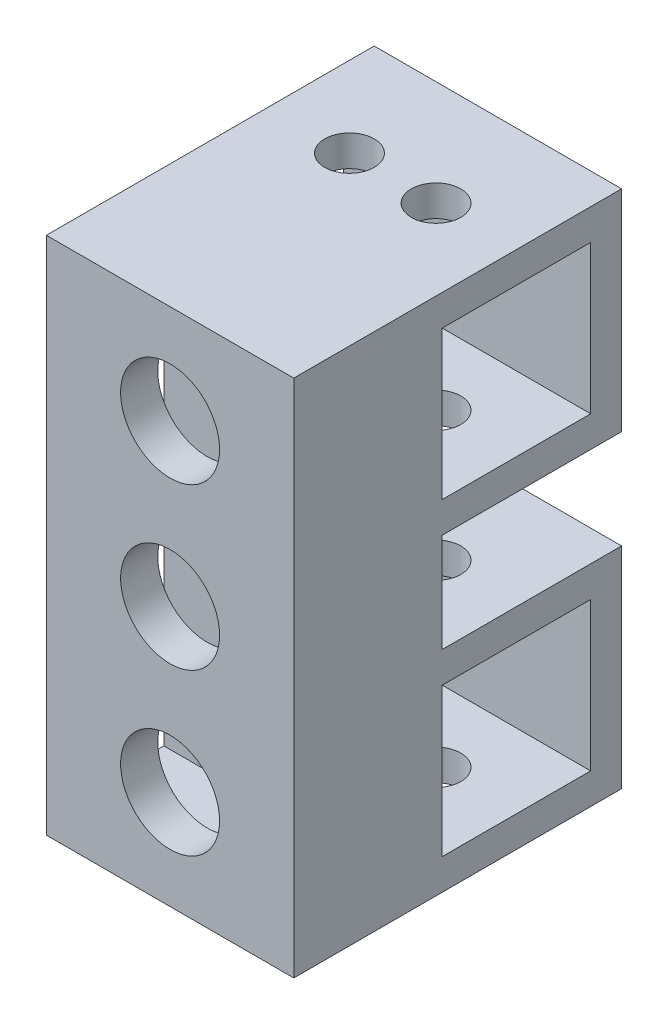
SolidWorks part; units mm, degrees
ref_plane "Plan de face" through (0, 0, 0) normal (0, 0, 1) x (1, 0, 0)
ref_plane "Plan de dessus" through (0, 0, 0) normal (0, 1, 0) x (1, 0, 0)
ref_plane "Plan de droite" through (0, 0, 0) normal (1, 0, 0) x (0, 0, -1)
sketch "Esquisse1" plane through (0, 0, 0) normal (0, 0, 1) x (1, 0, 0)
  line L0 (0, -49.5) -> (0, -41.5)
  line L1 (0, 0) -> (20, 0)
  line L2 (0, 0) -> (0, -42)
  line L3 (0, -42) -> (20, -42)
  line L4 (20, 0) -> (20, -42)
  line L6 (20, 0) -> (20, -42)
  line L7 (20, -10.5) -> (20, -18.5)
  line L11 (0, -10.5) -> (0, -18.5)
  line L15 (20, -41.5) -> (20, -49.5)
  line L19 (0, -41.5) -> (0, -49.5)
  line L22 (0, -18.5) -> (0, -10.5)
  line L23 (20, -10.5) -> (20, -18.5)
  line L24 (20, -41.5) -> (20, -49.5)
  line L25 (20, -49.5) -> (20.1497, -49.6465)
  dimension "D4" = 42
  dimension "D5" = 20
extrude "Boss.-Extru.1" add sketch "Esquisse1" along normal blind 12 contours L4 L1 L2 L3 | L4 | L4 | L4 | L0 | L2 region at (10, -21, 0)
sketch "Esquisse2" plane through (0, 0, 0) normal (0, 0, -1) x (-1, 0, 0)
  line L0 (0, -42) -> (-20, -42) construction
  line L1 (0, -42) -> (-20, -42)
  line L2 (0, -42) -> (0, -25)
  line L3 (0, -25) -> (-20, -25)
  line L4 (-20, -42) -> (-20, -25)
  line L5 (0, 0) -> (0, -42) construction
  line L6 (-20, 0) -> (-20, -42) construction
  line L8 (-20, 0) -> (-20, -42) construction
  point P6 (-20, -21)
  point P8 (-20, -33.5)
  dimension "D1" = 17
  dimension "D2" = 12.5
  dimension "D4" = 0
  dimension "D5" = 0
  dimension "D6" = 8.5
extrude "Boss.-Extru.3" add sketch "Esquisse2" along normal blind 14.5
sketch "Esquisse3" plane through (20, 0, 0) normal (1, 0, 0) x (0, 0, -1)
  line L0 (0, 0) -> (0, -25) construction
  line L1 (12, -39.5) -> (0, -39.5)
  line L2 (12, -39.5) -> (12, -27.5)
  line L3 (12, -27.5) -> (0, -27.5)
  line L4 (0, -39.5) -> (0, -27.5)
  line L5 (14.5, -42) -> (-12, -42) construction
  dimension "D1" = 12
  dimension "D2" = 12
  dimension "D3" = 0
  dimension "D4" = 2.5
extrude "Enlèv. mat.-Extru.3" cut sketch "Esquisse3" against normal through all
ref_plane "Plan1" through (0, -21, 0) normal (0, -1, 0) x (-1, 0, 0)
mirror "Symétrie1" about plane through (0, -21, 0) normal (0, -1, 0) of "Boss.-Extru.3", "Enlèv. mat.-Extru.3"
sketch "Esquisse4" plane through (0, -42, 0) normal (0, -1, 0) x (1, 0, 0)
  line L1 (0, -12) -> (20, -12) construction
  line L2 (20, -14.5) -> (0, -14.5) construction
  circle A0 centre (13.5, -6) radius 2
  circle A1 centre (6.5, -6) radius 2
  point P10 (10, -14.5)
  dimension "D1" = 6
  dimension "D3" = 4
  dimension "D4" = 4
  dimension "D2" = 3.5
  dimension "D5" = 7
  dimension "D6" = 8.5
extrude "Enlèv. mat.-Extru.4" cut sketch "Esquisse4" against normal blind 42
ref_plane "Plan2" through (10, 0, 0) normal (-1, 0, 0) x (0, 0, 1)
sketch "Esquisse5" plane through (0, 0, 12) normal (0, 0, 1) x (1, 0, 0)
  line L0 (0, -42) -> (20, -42) construction
  line L1 (6.2472, -40.5) -> (13.7528, -40.5)
  line L2 (13.7528, -40.5) -> (17.5056, -34)
  line L3 (17.5056, -34) -> (13.7528, -27.5)
  line L4 (13.7528, -27.5) -> (6.2472, -27.5)
  line L5 (6.2472, -27.5) -> (2.4944, -34)
  line L6 (2.4944, -34) -> (6.2472, -40.5)
  line L7 (13.7528, -14.5) -> (17.5056, -8)
  line L8 (17.5056, -8) -> (13.7528, -1.5)
  line L9 (13.7528, -1.5) -> (6.2472, -1.5)
  line L10 (6.2472, -1.5) -> (2.4944, -8)
  line L11 (2.4944, -8) -> (6.2472, -14.5)
  line L12 (6.2472, -14.5) -> (13.7528, -14.5)
  line L13 (6.2472, -14.5) -> (2.4944, -21)
  line L14 (2.4944, -21) -> (6.2472, -27.5)
  line L15 (6.2472, -27.5) -> (13.7528, -27.5)
  line L16 (13.7528, -27.5) -> (17.5056, -21)
  line L17 (17.5056, -21) -> (13.7528, -14.5)
  line L18 (13.7528, -14.5) -> (6.2472, -14.5)
  line L19 (-11, -21) -> (11, -21) construction
  line L20 (10, 14.575) -> (10, -14.575) construction
  line L21 (6.2472, -40.5) -> (0, -40.5)
  line L22 (0, 0) -> (0, -42) construction
  line L23 (0, -40.5) -> (0, -1.5)
  line L24 (0, -1.5) -> (6.2472, -1.5)
  circle A0 centre (10, -34) radius 6.5 construction
  circle A1 centre (10, -8) radius 6.5 construction
  circle A2 centre (10, -21) radius 6.5 construction
  line M9 (0, 0) -> (0, -42)
  dimension "D1" = 13
  dimension "D2" = 13
  dimension "D3" = 13
  dimension "D4" = 0
  dimension "D5" = 0
  dimension "D6" = 360
  dimension "D7" = 0
  dimension "D8" = 6.5
  dimension "D9" = 0
  dimension "D10" = 0
  dimension "D11" = 0
  dimension "D12" = 13
  dimension "D13" = 180
extrude "Enlèv. mat.-Extru.5" cut sketch "Esquisse5" against normal blind 6.5 from offset 3 contours L16 L17 L12 L13 L14 L4 | L5 L6 L1 L2 L3 L4 | L24 L21 L6 L5 L14 L13 L11 L10 M9 | L11 L12 L7 L8 L9 L10 region at (10, -34, 12) region at (2.3197, -21, 12) region at (10, -21, 12) region at (10, -8, 12) offset against normal yes
sketch "Esquisse6" plane through (0, 0, 12) normal (0, 0, 1) x (1, 0, 0)
  circle A0 centre (10, -34) radius 4
  circle A1 centre (10, -21) radius 4
  circle A2 centre (10, -8) radius 4
  dimension "D1" = 8
  dimension "D2" = 8
  dimension "D3" = 8
extrude "Enlèv. mat.-Extru.6" cut sketch "Esquisse6" against normal blind 13.5
equation "\"é\"=1.5583"
equation "\"à\"=2.55842"
equation "\"éà\"=42"
